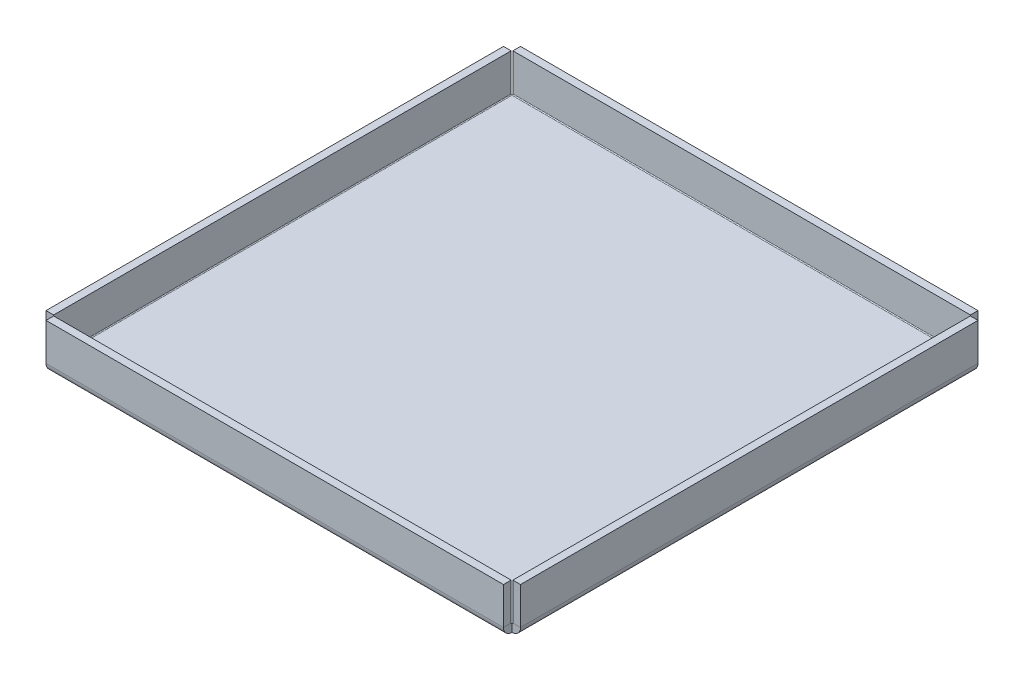
SolidWorks part; units mm, degrees
note: The reader was unsure of these and kept them because the rebuilt part matched: flange length of "Edge-Flange3", "Edge-Flange4", "Edge-Flange5", "Edge-Flange6".
material "Polyester Resin"
ref_plane "Front Plane" through (0, 0, 0) normal (0, 0, 1) x (1, 0, 0)
ref_plane "Top Plane" through (0, 0, 0) normal (0, 1, 0) x (1, 0, 0)
ref_plane "Right Plane" through (0, 0, 0) normal (1, 0, 0) x (0, 0, -1)
sketch "Sketch1" plane through (0, 0, 0) normal (0, 1, 0) x (1, 0, 0)
  line L1 (0, 0) -> (381, 0)
  line L2 (0, 0) -> (0, 381)
  line L3 (0, 381) -> (381, 381)
  line L4 (381, 0) -> (381, 381)
  dimension "D1" = 381
  dimension "D2" = 381
base flange "Base-Flange1" sketch "Sketch1" thickness 6.35 reverse thickness direction no parameters "D1"=0.7366
edge flange "Edge-Flange3" sketch "Sketch14" flange angle 90 flange length 38.1 flange position bend outside bend radius 0.7366 thickness 6.35 relief rectangular parameters "D6"=10
sketch "Sketch14" plane through (0, 0, 0) normal (-1, 0, 0) x (0, 0, 1)
  line L2 (-381, 0) -> (-381, 31.75)
  line L3 (-381, 31.75) -> (0, 31.75)
  line L4 (0, 31.75) -> (0, 0)
  line L9 (-381, 0) -> (0, 0) construction
  line L10 (-381, 0) -> (0, 0)
bend "EdgeBend3" bend radius 0.7366 bend angle 90 parameters "D5"=3
edge flange "Edge-Flange4" sketch "Sketch17" flange angle 90 flange length 38.1 flange position bend outside bend radius 0.7366 thickness 6.35 relief rectangular parameters "D6"=10
sketch "Sketch17" plane through (0, 0, -381) normal (0, 0, -1) x (-1, 0, 0)
  line L2 (-381, 0) -> (-381, 31.75)
  line L3 (-381, 31.75) -> (0, 31.75)
  line L4 (0, 31.75) -> (0, 0)
  line L5 (-381, 0) -> (0, 0) construction
  line L6 (-381, 0) -> (0, 0)
bend "EdgeBend4" bend radius 0.7366 bend angle 90 parameters "D5"=4
edge flange "Edge-Flange5" sketch "Sketch20" flange angle 90 flange length 38.1 flange position bend outside bend radius 0.7366 thickness 6.35 relief rectangular parameters "D6"=10
sketch "Sketch20" plane through (0, 0, 0) normal (0, 0, 1) x (1, 0, 0)
  line L2 (0, 0) -> (0, 31.75)
  line L3 (0, 31.75) -> (381, 31.75)
  line L4 (381, 31.75) -> (381, 0)
  line L5 (0, 0) -> (381, 0) construction
  line L6 (0, 0) -> (381, 0)
bend "EdgeBend5" bend radius 0.7366 bend angle 90 parameters "D5"=5
edge flange "Edge-Flange6" sketch "Sketch23" flange angle 90 flange length 38.1 flange position bend outside bend radius 0.7366 thickness 6.35 relief rectangular parameters "D6"=10
sketch "Sketch23" plane through (381, 0, 0) normal (1, 0, 0) x (0, 0, -1)
  line L0 (0, 0) -> (381, 0) construction
  line L1 (0, 0) -> (381, 0)
  line L2 (0, 0) -> (0, 31.75)
  line L3 (0, 31.75) -> (381, 31.75)
  line L4 (381, 31.75) -> (381, 0)
bend "EdgeBend6" bend radius 0.7366 bend angle 90 parameters "D5"=6
sketch "Bend-Lines1" [suppressed] plane through (0, 0, 0) normal (0, 1, 0) x (1, 0, 0)
sketch "Bounding-Box1" [suppressed] plane through (0, 0, 0) normal (0, 1, 0) x (1, 0, 0)
sheet metal parameters "Sheet-Metal1" thickness 6.35 parameters "D1"=0.7366
flat pattern "Flat-Pattern1" [suppressed]
sketch "Bend-Lines2" plane through (0, 0, 0) normal (0, 1, 0) x (1, 0, 0)
sketch3d "Bounding-Box2" [suppressed]
  line L0 (0, 0, 0) -> (0, 381, 0) construction
  line L1 (-381, 0, 0) -> (-381, 381, 0) construction
  line L2 (0, 0, 0) -> (-381, 0, 0) construction
  line L3 (0, 381, 0) -> (-381, 381, 0) construction
sheet metal parameters "Sheet-Metal4" thickness 6.35 parameters "D1"=0.7366
flat pattern "Flat-Pattern1"
sketch "Bend-Lines2" plane through (0, 0, 0) normal (0, 1, 0) x (1, 0, 0)
  line L4 (-2.3356, 381) -> (-2.3356, 0) construction
  line L5 (-2.3356, 381) -> (-2.3356, 0) construction
  point P2 (381, 383.3356)
  point P3 (0, 383.3356)
sketch3d "Bounding-Box2" [suppressed]
  line L0 (381, 381, 0) -> (-36.4211, 381, 0) construction
  line L1 (381, 0, 0) -> (-36.4211, 0, 0) construction
  line L2 (381, 381, 0) -> (381, 0, 0) construction
  line L3 (-36.4211, 381, 0) -> (-36.4211, 0, 0) construction
bend of the flat pattern "Flatten-<EdgeBend3>1"
sheet metal parameters "Sheet-Metal5" thickness 6.35 parameters "D1"=0.7366
flat pattern "Flat-Pattern1"
sketch "Bend-Lines2" plane through (0, 0, 0) normal (0, 1, 0) x (1, 0, 0)
  line L0 (381, 383.3356) -> (0.7366, 383.3356) construction
  line L1 (381, 383.3356) -> (0.7366, 383.3356) construction
  line L4 (-2.3356, 381) -> (-2.3356, 0) construction
  line L5 (-2.3356, 381) -> (-2.3356, 0) construction
sketch3d "Bounding-Box2" [suppressed]
  line L0 (381, 417.4211, 0) -> (-36.4211, 417.4211, 0) construction
  line L1 (381, 0, 0) -> (-36.4211, 0, 0) construction
  line L2 (381, 417.4211, 0) -> (381, 0, 0) construction
  line L3 (-36.4211, 417.4211, 0) -> (-36.4211, 0, 0) construction
bend of the flat pattern "Flatten-<EdgeBend3>1"
bend of the flat pattern "Flatten-<EdgeBend4>1"
sheet metal parameters "Sheet-Metal6" thickness 6.35 parameters "D1"=0.7366
flat pattern "Flat-Pattern1"
sketch "Bend-Lines2" plane through (0, 0, 0) normal (0, 1, 0) x (1, 0, 0)
  line L0 (381, 383.3356) -> (0.7366, 383.3356) construction
  line L1 (381, 383.3356) -> (0.7366, 383.3356) construction
  line L2 (0.7366, -2.3356) -> (381, -2.3356) construction
  line L3 (0.7366, -2.3356) -> (381, -2.3356) construction
  line L4 (-2.3356, 381) -> (-2.3356, 0) construction
  line L5 (-2.3356, 381) -> (-2.3356, 0) construction
sketch3d "Bounding-Box2" [suppressed]
  line L0 (-36.4211, -36.4211, 0) -> (-36.4211, 417.4211, 0) construction
  line L1 (381, -36.4211, 0) -> (381, 417.4211, 0) construction
  line L2 (-36.4211, -36.4211, 0) -> (381, -36.4211, 0) construction
  line L3 (-36.4211, 417.4211, 0) -> (381, 417.4211, 0) construction
bend of the flat pattern "Flatten-<EdgeBend3>1"
bend of the flat pattern "Flatten-<EdgeBend4>1"
bend of the flat pattern "Flatten-<EdgeBend5>1"
sheet metal parameters "Sheet-Metal7" thickness 6.35 parameters "D1"=0.7366
flat pattern "Flat-Pattern1"
sketch "Bend-Lines2" plane through (0, 0, 0) normal (0, 1, 0) x (1, 0, 0)
  line L0 (381, 384.0722) -> (0, 384.0722) construction
  line L1 (381, 384.0722) -> (0, 384.0722) construction
  line L2 (0, -3.0722) -> (381, -3.0722) construction
  line L3 (0, -3.0722) -> (381, -3.0722) construction
  line L4 (-3.0722, 381) -> (-3.0722, 0) construction
  line L5 (-3.0722, 381) -> (-3.0722, 0) construction
  line L6 (384.0722, 0) -> (384.0722, 381) construction
  line L7 (384.0722, 0) -> (384.0722, 381) construction
sketch3d "Bounding-Box2" [suppressed]
  line L0 (-37.1577, -37.1577, 0) -> (-37.1577, 418.1577, 0) construction
  line L1 (418.1577, -37.1577, 0) -> (418.1577, 418.1577, 0) construction
  line L2 (-37.1577, -37.1577, 0) -> (418.1577, -37.1577, 0) construction
  line L3 (-37.1577, 418.1577, 0) -> (418.1577, 418.1577, 0) construction
bend of the flat pattern "Flatten-<EdgeBend3>1"
bend of the flat pattern "Flatten-<EdgeBend4>1"
bend of the flat pattern "Flatten-<EdgeBend5>1"
bend of the flat pattern "Flatten-<EdgeBend6>1"
